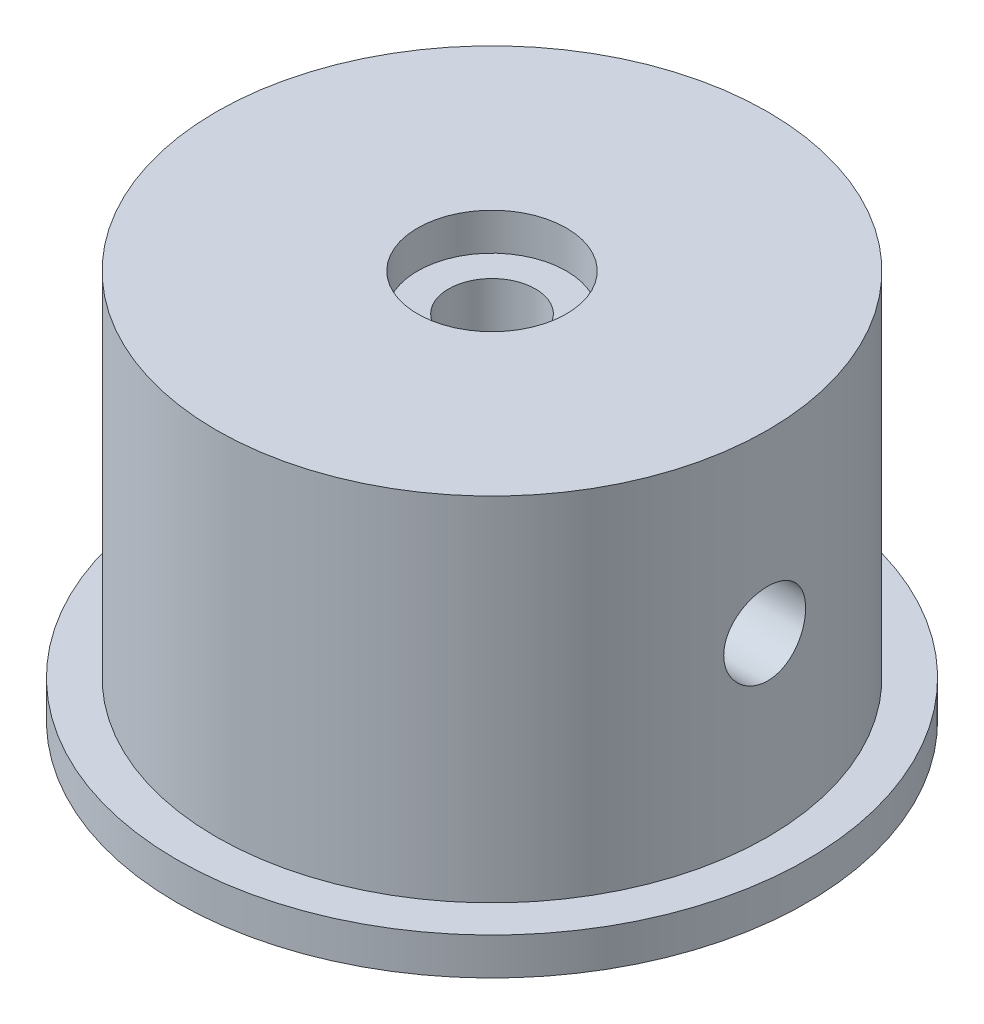
SolidWorks part; units mm, degrees
material "ABS"
ref_plane "Front Plane" through (0, 0, 0) normal (0, 0, 1) x (1, 0, 0)
ref_plane "Top Plane" through (0, 0, 0) normal (0, 1, 0) x (1, 0, 0)
ref_plane "Right Plane" through (0, 0, 0) normal (1, 0, 0) x (0, 0, -1)
sketch "Sketch1" plane through (0, 0, 0) normal (1, 0, 0) x (0, 0, -1)
  line L0 (-1.75, 0) -> (-3, 0)
  line L1 (-3, 0) -> (-3, -1.5)
  line L2 (-3, -1.5) -> (-12.7, -1.5)
  line L3 (-12.7, -1.5) -> (-12.7, 0)
  line L4 (-12.7, 0) -> (-11.1125, 0)
  line L5 (-11.1125, 0) -> (-11.1125, 14.2)
  line L6 (-11.1125, 14.2) -> (-3, 14.2)
  line L7 (-3, 14.2) -> (-3, 12.7)
  line L8 (-3, 12.7) -> (-1.75, 12.7)
  line L9 (-1.75, 12.7) -> (-1.75, 0)
  line L10 (0, -1000) -> (0, 49000) construction
  dimension "D1" = 12.7
  dimension "D2" = 11.1125
  dimension "D3" = 3
  dimension "D4" = 12.7
  dimension "D5" = 1.75
  dimension "D6" = 1.5
  dimension "D7" = 1.5
revolve "Revolve1" add sketch "Sketch1" angle 360 about L10
sketch "Sketch2" plane through (0, 0, 0) normal (1, 0, 0) x (0, 0, -1)
  line L0 (0, 0) -> (0, 14.2) construction
  line L1 (3, 14.2) -> (-3, 14.2) construction
  circle A0 centre (0, 7.1) radius 1.65
  point P2 (0, 0)
  point P8 (0, 7.1)
  point P9 (0, 0)
  dimension "D1" = 3.3
extrude "Cut-Extrude1" cut sketch "Sketch2" against normal up to next from offset 5 offset against normal yes
mirror "Mirror1" about plane through (0, 0, 0) normal (1, 0, 0) of "Cut-Extrude1"
